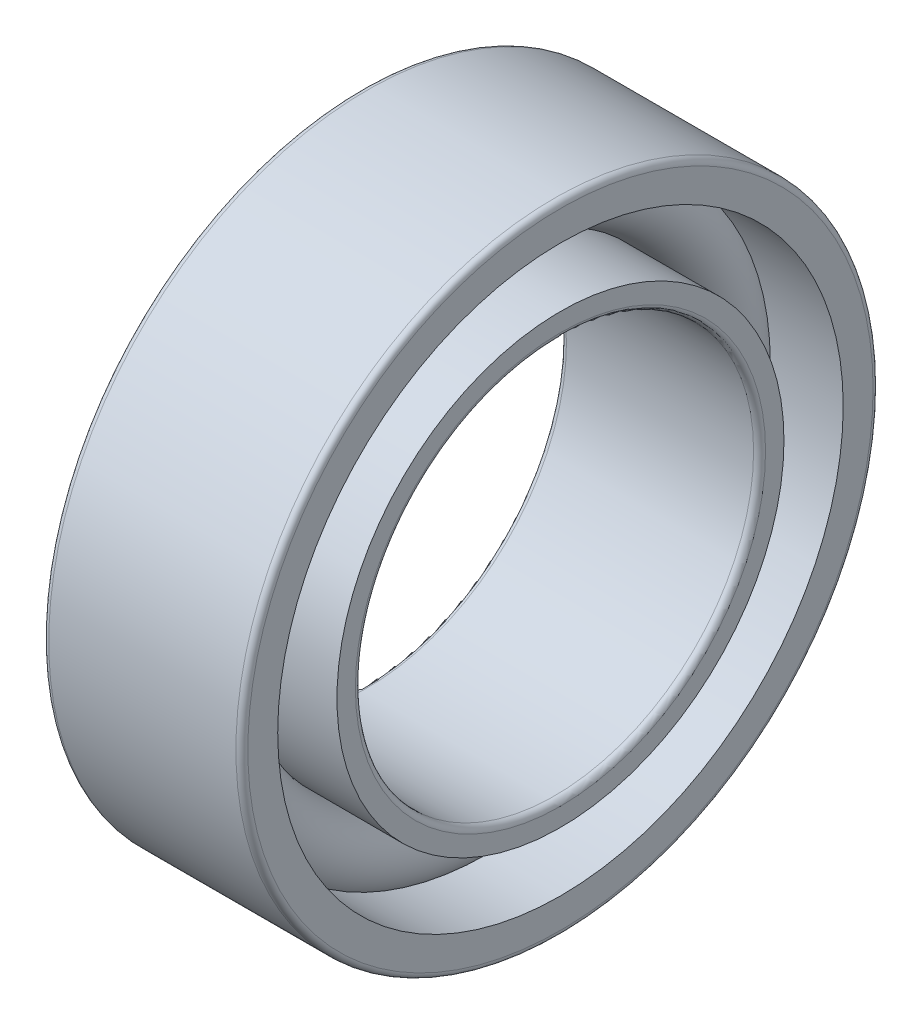
SolidWorks part; units mm, degrees
ref_plane "Plane1" through (0, 0, 0) normal (0, 0, 1) x (1, 0, 0)
ref_plane "Plane2" through (0, 0, 0) normal (0, 1, 0) x (1, 0, 0)
ref_plane "Plane3" through (0, 0, 0) normal (1, 0, 0) x (0, 0, -1)
sketch "Clipboard" plane through (0, 0, 0) normal (0, 0, 1) x (1, 0, 0)
  line L0 (-10, 0) -> (10, 0) construction
  line L1 (0, 0) -> (22.3471, -0.7804)
  line L2 (0, 0) -> (12.9921, 0.4537)
  line L3 (0, 0) -> (22.3471, -0.7804)
  line L4 (0, 0) -> (-22.3573, -0.3902)
  dimension "BallCLRad" = 13
sketch "CagSpiSke" plane through (0, 0, 0) normal (0, 0, 1) x (1, 0, 0)
  line L0 (0.45, 12.7) -> (0.45, 13.3)
  line L1 (0.45, 13.3) -> (-0.45, 13.3)
  line L2 (-0.45, 13.3) -> (-0.45, 12.7)
  line L3 (-0.45, 12.7) -> (0.45, 12.7)
  line L4 (-20.6375, 0) -> (20.6375, 0) construction
  line L5 (0, 0) -> (0, 23.7692) construction
  dimension "OD" = 26.6
  dimension "ID" = 25.4
revolve "CageSpine" add sketch "CagSpiSke" angle 0.001 about L4
ref_axis "Axis1" through (-50, 0, 0) along (1, 0, 0)
sketch "CagBalSke" plane through (0, 0, 0) normal (0, 0, 1) x (1, 0, 0)
  line L0 (-1.98, 13) -> (1.98, 13)
  line L1 (-1.905, 13) -> (1.905, 13) construction
  line L2 (-10, 0) -> (10, 0) construction
  line L3 (0, 0) -> (0, 24) construction
  arc A0 (1.98, 13) -> (-1.98, 13) centre (0, 13) cw
  dimension "BallCLRad" = 13
revolve "CageBall" [suppressed] add sketch "CagBalSke" angle 360 about L1 reverse direction yes
pattern_circular "CageBalls" [suppressed] count 2 every 180 about axis through (-50, 0, 0) along (1, 0, 0)
sketch "CagTrmODSke" plane through (0, 0, 0) normal (0, 0, 1) x (1, 0, 0)
  line L0 (1.981, 13.3) -> (1.981, 14.981)
  line L1 (1.981, 14.981) -> (-1.981, 14.981)
  line L2 (-1.981, 14.981) -> (-1.981, 13.3)
  line L3 (-1.981, 13.3) -> (1.981, 13.3)
  line L4 (-20.6375, 0) -> (20.6375, 0) construction
  line L5 (0, 0) -> (0, 25) construction
  dimension "Width" = 3.962
  dimension "ID" = 26.6
  dimension "OD" = 29.962
revolve "CageTrimOD" [suppressed] cut sketch "CagTrmODSke" angle 360 about L4 reverse direction yes
sketch "CagTrmIDSke" plane through (0, 0, 0) normal (0, 0, 1) x (1, 0, 0)
  line L0 (1.981, 11.021) -> (1.981, 12.7)
  line L1 (1.981, 12.7) -> (-1.981, 12.7)
  line L2 (-1.981, 12.7) -> (-1.981, 11.021)
  line L3 (-1.981, 11.021) -> (1.981, 11.021)
  line L4 (-20.6375, 0) -> (20.6375, 0) construction
  line L5 (0, 0) -> (0, 25) construction
  dimension "Width" = 3.962
  dimension "ID" = 22.042
  dimension "OD" = 25.4
revolve "CageTrimID" [suppressed] cut sketch "CagTrmIDSke" angle 360 about L4 reverse direction yes
sketch "BalSimSke" plane through (0, 0, 0) normal (0, 0, 1) x (1, 0, 0)
  line L0 (-10, 0) -> (10, 0) construction
  line L1 (-10, 13) -> (10, 13) construction
  line L2 (0, 0) -> (0, 23) construction
  circle A0 centre (0, 13) radius 1.8
  dimension "BallCLRad" = 13
  dimension "Ball_diameter" = 3.6
revolve "BallsSimplified" add sketch "BalSimSke" angle 360 about L0
sketch "BalDetSke" plane through (0, 0, 0) normal (0, 0, 1) x (1, 0, 0)
  line L0 (-1.8, 13) -> (1.8, 13)
  line L1 (-1.905, 13) -> (1.905, 13) construction
  line L2 (0, 0) -> (0, 25) construction
  arc A0 (1.8, 13) -> (-1.8, 13) centre (0, 13) cw
  dimension "BallCLRad" = 13
  dimension "Ball_diameter" = 3.6
revolve "BallDetailed" [suppressed] add sketch "BalDetSke" angle 360 about L1 reverse direction yes
sketch "InnRacSke" plane through (0, 0, 0) normal (0, 0, 1) x (1, 0, 0)
  line L0 (-1.3079, 11.8) -> (-5, 11.8)
  line L1 (-5, 11.8) -> (-5, 10.3)
  line L2 (-4.7, 10) -> (4.7, 10)
  line L3 (5, 10.3) -> (5, 11.225)
  line L4 (0, 11.225) -> (5, 11.225)
  line L5 (-20.6375, 0) -> (20.6375, 0) construction
  line L6 (0, 0) -> (0, 30) construction
  arc A0 (-5, 10.3) -> (-4.7, 10) centre (-4.7, 10.3) ccw
  arc A1 (4.7, 10) -> (5, 10.3) centre (4.7, 10.3) ccw
  arc A2 (0, 11.225) -> (-1.3079, 11.8) centre (0, 13) cw
  dimension "BallCLRad" = 13
  dimension "Fillet_radius" = 0.3
  dimension "Ball_diameter" = 3.55
  dimension "ID" = 20
  dimension "OD" = 23.6
  dimension "Width" = 10
revolve "InnerRace" add sketch "InnRacSke" angle 360 about L5 reverse direction yes
sketch "OutRacSke" plane through (0, 0, 0) normal (0, 0, 1) x (1, 0, 0)
  line L0 (0, 14.775) -> (-5, 14.775)
  line L1 (-5, 14.775) -> (-5, 15.7)
  line L2 (-4.7, 16) -> (4.7, 16)
  line L3 (5, 15.7) -> (5, 14.2)
  line L4 (5, 14.2) -> (1.3079, 14.2)
  line L5 (-20.6375, 0) -> (20.6375, 0) construction
  line L6 (0, 0) -> (0, 30) construction
  arc A0 (-5, 15.7) -> (-4.7, 16) centre (-4.7, 15.7) cw
  arc A1 (4.7, 16) -> (5, 15.7) centre (4.7, 15.7) cw
  arc A2 (1.3079, 14.2) -> (0, 14.775) centre (0, 13) ccw
  dimension "BallCLRad" = 13
  dimension "Fillet_radius" = 0.3
  dimension "Ball_diameter" = 3.55
  dimension "Width" = 10
revolve "OuterRace" add sketch "OutRacSke" angle 360 about L5 reverse direction yes
pattern_circular "BallsDetailed" [suppressed] count 2 every 180 about axis through (-50, 0, 0) along (1, 0, 0)
equation "\"BallCLRad@Clipboard\" = ( \"OD@OutRacSke\" + \"ID@InnRacSke\" ) / 4"
equation "\"BallCLRad@BalSimSke\" = \"BallCLRad@Clipboard\""
equation "\"BallCLRad@BalDetSke\" = \"BallCLRad@Clipboard\""
equation "\"BallCLRad@InnRacSke\" = \"BallCLRad@Clipboard\""
equation "\"BallCLRad@OutRacSke\" = \"BallCLRad@Clipboard\""
equation "\"Ball_diameter@InnRacSke\" = \"Ball_diameter@BalDetSke\" - 0.05"
equation "\"Ball_diameter@OutRacSke\" = \"Ball_diameter@BalDetSke\" - 0.05"
equation "\"Ball_diameter@BalSimSke\" = \"Ball_diameter@BalDetSke\""
equation "\"Width@OutRacSke\" = \"Width@InnRacSke\""
equation "\"Fillet_radius@OutRacSke\" = \"Fillet_radius@InnRacSke\""
equation "\"Max_count@Clipboard\" = int( 3.14159265 / atn(( \"Ball_diameter@BalDetSke\" / 2) / sqr( \"BallCLRad@Clipboard\"  *  \"BallCLRad@Clipboard\" - ( \"Ball_diameter@BalDetSke\" / 2) *  ( \"Ball_diameter@BalDetSke\" / 2))))"
equation "\"Max_count@Clipboard\" = ((sgn( \"Max_count@Clipboard\" - \"Count@Clipboard\" )-1)*( \"Max_count@Clipboard\" - \"Count@Clipboard\" ))/-2+ \"Count@Clipboard\""
equation "\"Count@BallsDetailed\" = int( \"Show_count@Clipboard\" ) "
equation "\"Count@BallsDetailed\" = ((sgn( \"Count@BallsDetailed\" - \"Max_count@Clipboard\" )-1)*( \"Count@BallsDetailed\" - \"Max_count@Clipboard\" ))/-2+ \"Max_count@Clipboard\""
equation "\"Count@BallsDetailed\" = ((sgn( \"Count@BallsDetailed\" - \"Min_count@Clipboard\" )+1)*( \"Count@BallsDetailed\" - \"Min_count@Clipboard\"))/2 +\"Min_count@Clipboard\""
equation "\"Angle@BallsDetailed\" = 360.0 / \"Max_count@Clipboard\""
equation "\"BallCLRad@CagBalSke\" = \"BallCLRad@Clipboard\""
equation "\"Count@CageBalls\" = \"Count@BallsDetailed\""
equation "\"Angle@CageBalls\" = \"Angle@BallsDetailed\""
equation "\"Angle@CageSpine\" =  \"Angle@CageBalls\" * ( \"Count@CageBalls\" -1 + int( \"Count@CageBalls\" / \"Max_count@Clipboard\" ) )  + 0.001 -  int( \"Count@CageBalls\" / \"Max_count@Clipboard\" ) * 0.001"
equation "\"Angle@CageSpine\" =  \"Angle@CageSpine\" * int( \"Min_count@Clipboard\" / 2) + int(1 / \"Min_count@Clipboard\")  * 0.001"
equation "\"CageWallOD@CagBalSke\" =  \"Ball_diameter@BalDetSke\" * 1.1"
equation "\"Thickness@CagSpiSke\" =  \"Ball_diameter@BalDetSke\" * 0.25"
equation "\"OD@CagTrmODSke\" = \"BallCLRad@Clipboard\" * 2 + \"CageWallOD@CagBalSke\" + 0.002"
equation "\"ID@CagTrmODSke\" = \"BallCLRad@Clipboard\" * 2 + \"Ball_diameter@BalDetSke\" / 6"
equation "\"OD@CagTrmIDSke\" = \"BallCLRad@Clipboard\" * 2 - \"Ball_diameter@BalDetSke\" / 6"
equation "\"ID@CagTrmIDSke\" = \"BallCLRad@Clipboard\" * 2 - \"CageWallOD@CagBalSke\" + 0.002"
equation "\"OD@CagSpiSke\" = \"ID@CagTrmODSke\""
equation "\"ID@CagSpiSke\" = \"OD@CagTrmIDSke\""
equation "\"Width@CagTrmODSke\" = \"CageWallOD@CagBalSke\" + 0.002"
equation "\"Width@CagTrmIDSke\" = \"CageWallOD@CagBalSke\" + 0.002"
